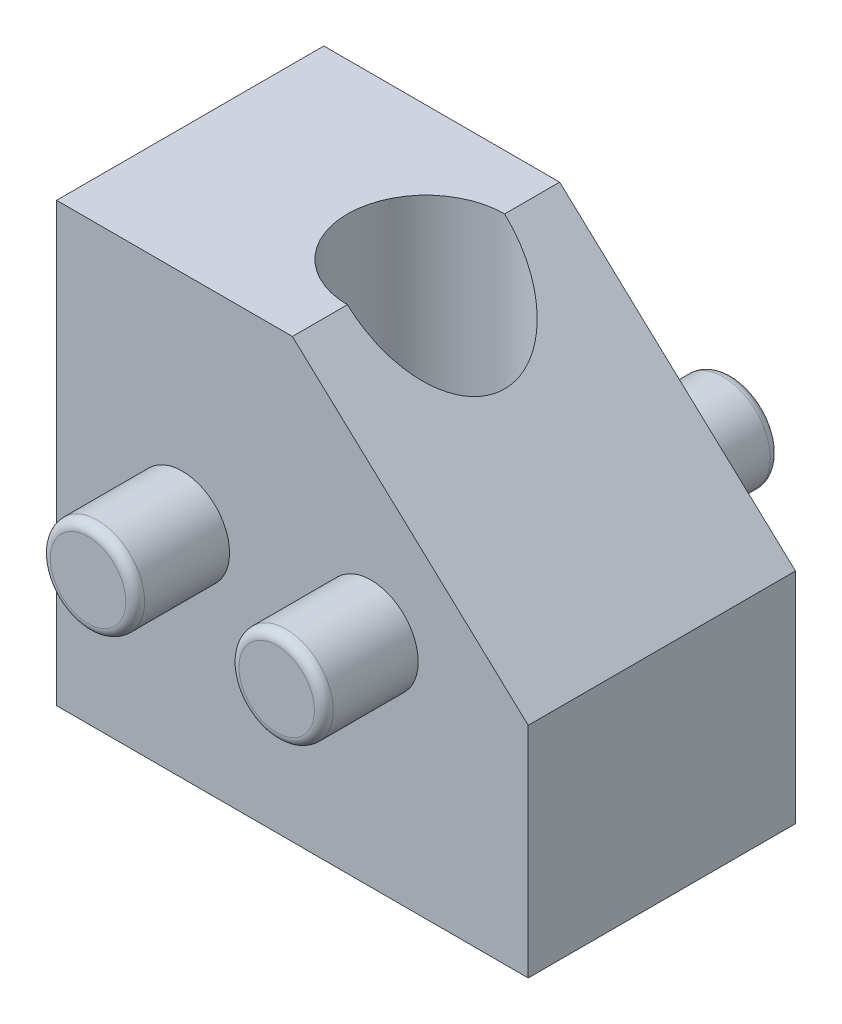
SolidWorks part; units mm, degrees
ref_plane "정면" through (0, 0, 0) normal (0, 0, 1) x (1, 0, 0)
ref_plane "윗면" through (0, 0, 0) normal (0, 1, 0) x (1, 0, 0)
ref_plane "우측면" through (0, 0, 0) normal (1, 0, 0) x (0, 0, -1)
sketch "스케치1" plane through (0, 0, 0) normal (0, 0, 1) x (1, 0, 0)
  line L0 (-6.0605, 5.6241) -> (1.4395, 5.6241)
  line L1 (8.9395, -1.3359) -> (8.9395, -8.2959)
  line L2 (-6.0605, 5.6241) -> (-6.0605, -8.2959)
  line L3 (-6.0605, -8.2959) -> (8.9395, -8.2959)
  line L4 (8.9395, -1.3359) -> (1.4395, 5.6241)
  circle A0 centre (-2.0605, -1.3359) radius 1.5
  circle A1 centre (3.9395, -1.3359) radius 1.5
  point P0 (0, 0)
  dimension "D3" = 3
  dimension "D4" = 3
  dimension "D1" = 13.92
  dimension "D2" = 15
  dimension "D5" = 4
  dimension "D6" = 6
  dimension "D7" = 6.96
extrude "보스-돌출1" add sketch "스케치1" along normal blind 8.5 contours A1 | L1 L4 L0 L2 L3 A1 A0 | A0 region at (0.7073, -2.0543, 0) region at (-2.0605, -1.3359, 0) region at (3.9395, -1.3359, 0)
extrude "보스-돌출2" add sketch "스케치1<3>" against normal blind 3 contours A1 | A0 region at (-2.0605, -1.3359, 0) region at (3.9395, -1.3359, 0)
sketch "스케치1<3>" plane through (0, 0, 0) normal (0, 0, 1) x (1, 0, 0) same geometry as "스케치1"
extrude "보스-돌출3" add sketch "스케치1<4>" along normal blind 11.5 contours A0 | A1
sketch "스케치1<4>" plane through (0, 0, 0) normal (0, 0, 1) x (1, 0, 0) same geometry as "스케치1"
sketch "스케치2" plane through (0, -8.2959, 0) normal (0, -1, 0) x (1, 0, 0)
  line L0 (-6.0605, 8.5) -> (8.9395, 0) construction
  circle A0 centre (1.4395, 4.25) radius 3.0277
hole_wizard "M6 탭을 위한 탭 드릴1" positions "3D스케치1" profile "스케치4" hole size "M6" standard "KS" end condition up to next
sketch3d "3D스케치1"
  point P0 (1.4395, -8.2959, 4.25)
sketch "스케치4" plane through (1.4395, -8.2959, 4.25) normal (1, 0, 0) x (0, 0, -1)
  line L0 (0, 0) -> (0, 13.92)
  line L1 (0, 13.92) -> (2.5, 13.92)
  line L2 (2.5, 13.92) -> (2.5, 0)
  line L5 (2.5, 0) -> (0, 0)
  line L11 (0, -6.35) -> (0, 107.95) construction
  dimension "관통 구멍 지름" = 5
  dimension "관통 구멍 깊이" = 13.92
fillet "필렛1" radius 0.3 4 edges at (5.4395, -1.3359, -3) (-0.5605, -1.3359, -3) (5.4395, -1.3359, 11.5) (-0.5605, -1.3359, 11.5)
